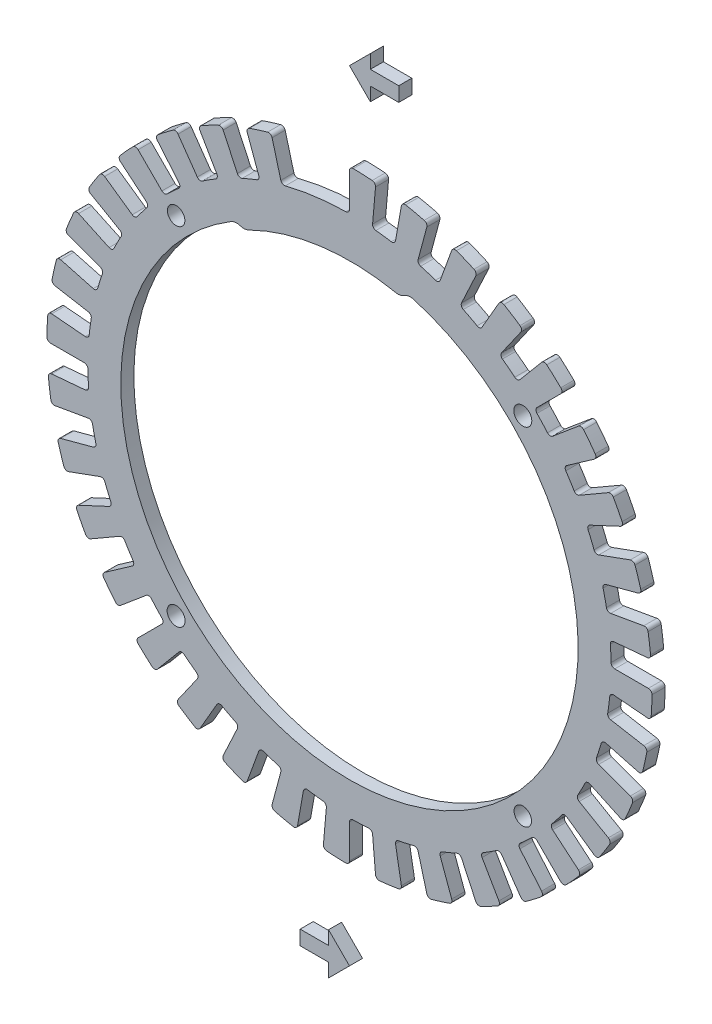
SolidWorks part; units mm, degrees
ref_plane "Front Plane" through (0, 0, 0) normal (0, 0, 1) x (1, 0, 0)
ref_plane "Top Plane" through (0, 0, 0) normal (0, 1, 0) x (1, 0, 0)
ref_plane "Right Plane" through (0, 0, 0) normal (1, 0, 0) x (0, 0, -1)
sketch "Sketch1" plane through (0, 0, 0) normal (0, 0, 1) x (1, 0, 0)
  line L0 (0, 82.7) -> (0, 71.5) construction
  line L1 (7.2078, 82.3853) -> (6.2316, 71.2279) construction
  line L2 (0, 71.5) -> (0, 0) construction
  line L3 (6.2316, 71.2279) -> (0, 0) construction
  line L4 (12.5883, 71.3918) -> (14.186, 80.4528) construction
  line L5 (12.5883, 71.3918) -> (0, 0) construction
  line L8 (0, 0) -> (47.3762, 47.3762) construction
  line L12 (50.5581, 50.5581) -> (47.3762, 47.3762) construction
  line L15 (47.3762, 47.3762) -> (44.1942, 44.1942) construction
  line L18 (7.3144, 72.1301) -> (6.3182, 72.2172) construction
  line L21 (7.3144, 72.1301) -> (7.2135, 71.1352) construction
  line L24 (12.5883, 71.3918) -> (11.6035, 71.5654) construction
  line L27 (11.6035, 71.5654) -> (11.4434, 70.5783) construction
  line L30 (1.0122, 82.6938) -> (1, 81.6939) construction
  line L33 (1, 81.6939) -> (0, 81.6939) construction
  line L36 (7.1201, 81.383) -> (6.1239, 81.4702) construction
  line L39 (6.1239, 81.4702) -> (6.1989, 82.4674) construction
  line L42 (7.1201, 81.383) -> (6.3182, 72.2172)
  line L45 (0, 81.6939) -> (0, 72.4931)
  line L48 (0, 72.4931) -> (-1, 72.4931) construction
  line L51 (-1, 72.4931) -> (-0.9862, 71.4932) construction
  line L109 (0, -82.7) -> (0, -71.5) [skipped]
  line L111 (14.3607, 81.4436) -> (12.4158, 70.4138) [skipped]
  line L115 (41.35, 71.6203) -> (35.75, 61.9208) [skipped]
  line L117 (53.1585, 63.3519) -> (45.9593, 54.7722) [skipped]
  line L118 (-63.3519, -53.1585) -> (-54.7722, -45.9593) [skipped]
  line L119 (63.3519, 53.1585) -> (54.7722, 45.9593) [skipped]
  line L121 (71.6203, 41.35) -> (61.9208, 35.75) [skipped]
  line L123 (77.7126, 28.2851) -> (67.188, 24.4544) [skipped]
  line L125 (81.4436, 14.3607) -> (70.4138, 12.4158) [skipped]
  line L127 (82.7, 0) -> (71.5, 0) [skipped]
  line L129 (81.4436, -14.3607) -> (70.4138, -12.4158) [skipped]
  line L131 (77.7126, -28.2851) -> (67.188, -24.4544) [skipped]
  line L133 (71.6203, -41.35) -> (61.9208, -35.75) [skipped]
  line L135 (63.3519, -53.1585) -> (54.7722, -45.9593) [skipped]
  line L137 (53.1585, -63.3519) -> (45.9593, -54.7722) [skipped]
  line L139 (41.35, -71.6203) -> (35.75, -61.9208) [skipped]
  line L141 (28.2851, -77.7126) -> (24.4544, -67.188) [skipped]
  line L142 (14.3607, -81.4436) -> (12.4158, -70.4138) [skipped]
  line L143 (34.9505, 74.9517) -> (30.2172, 64.801) [skipped]
  line L144 (47.4348, 67.7439) -> (41.0107, 58.5694) [skipped]
  line L145 (58.4777, 58.4777) -> (50.5581, 50.5581) [skipped]
  line L146 (67.7439, 47.4348) -> (58.5694, 41.0107) [skipped]
  line L147 (74.9517, 34.9505) -> (64.801, 30.2172) [skipped]
  line L148 (79.8821, 21.4043) -> (69.0637, 18.5056) [skipped]
  line L149 (82.3853, 7.2078) -> (71.2279, 6.2316) [skipped]
  line L150 (82.3853, -7.2078) -> (71.2279, -6.2316) [skipped]
  line L151 (79.8821, -21.4043) -> (69.0637, -18.5056) [skipped]
  line L152 (74.9517, -34.9505) -> (64.801, -30.2172) [skipped]
  line L153 (67.7439, -47.4348) -> (58.5694, -41.0107) [skipped]
  line L154 (58.4777, -58.4777) -> (50.5581, -50.5581) [skipped]
  line L155 (47.4348, -67.7439) -> (41.0107, -58.5694) [skipped]
  line L156 (34.9505, -74.9517) -> (30.2172, -64.801) [skipped]
  line L157 (21.4043, -79.8821) -> (18.5056, -69.0637) [skipped]
  line L158 (7.2078, -82.3853) -> (6.2316, -71.2279) [skipped]
  line L159 (-7.2078, -82.3853) -> (-6.2316, -71.2279) [skipped]
  line L160 (-21.4043, -79.8821) -> (-18.5056, -69.0637) [skipped]
  line L161 (-34.9505, -74.9517) -> (-30.2172, -64.801) [skipped]
  line L162 (-47.4348, -67.7439) -> (-41.0107, -58.5694) [skipped]
  line L163 (-58.4777, -58.4777) -> (-50.5581, -50.5581) [skipped]
  line L164 (-67.7439, -47.4348) -> (-58.5694, -41.0107) [skipped]
  line L165 (-74.9517, -34.9505) -> (-64.801, -30.2172) [skipped]
  line L166 (-79.8821, -21.4043) -> (-69.0637, -18.5056) [skipped]
  line L167 (-82.3853, -7.2078) -> (-71.2279, -6.2316) [skipped]
  line L168 (-82.3853, 7.2078) -> (-71.2279, 6.2316) [skipped]
  line L169 (-79.8821, 21.4043) -> (-69.0637, 18.5056) [skipped]
  line L170 (-74.9517, 34.9505) -> (-64.801, 30.2172) [skipped]
  line L171 (-67.7439, 47.4348) -> (-58.5694, 41.0107) [skipped]
  line L172 (-58.4777, 58.4777) -> (-50.5581, 50.5581) [skipped]
  line L173 (-47.4348, 67.7439) -> (-41.0107, 58.5694) [skipped]
  line L174 (-34.9505, 74.9517) -> (-30.2172, 64.801) [skipped]
  line L175 (-21.4043, 79.8821) -> (-18.5056, 69.0637) [skipped]
  line L176 (21.4043, 79.8821) -> (18.5056, 69.0637) [skipped]
  line L209 (0, 0) -> (-47.3762, -47.3762) construction
  line L210 (0, 0) -> (-47.3762, 47.3762) construction
  line L211 (0, 0) -> (47.3762, -47.3762) construction
  line L212 (14.186, 80.4528) -> (12.5883, 71.3918)
  line L213 (21.1439, 78.9102) -> (18.7626, 70.023)
  line L214 (27.941, 76.7671) -> (24.7941, 68.1212)
  line L215 (34.5253, 74.0398) -> (30.6369, 65.7011)
  line L216 (40.8469, 70.749) -> (36.2466, 62.7809)
  line L217 (46.8577, 66.9197) -> (41.5803, 59.3829)
  line L218 (52.5118, 62.5811) -> (46.5977, 55.5329)
  line L219 (57.7663, 57.7663) -> (51.2604, 51.2604)
  line L220 (62.5811, 52.5118) -> (55.5329, 46.5977)
  line L221 (66.9197, 46.8577) -> (59.3829, 41.5803)
  line L222 (70.749, 40.8469) -> (62.7809, 36.2466)
  line L223 (74.0398, 34.5253) -> (65.7011, 30.6369)
  line L224 (76.7671, 27.941) -> (68.1212, 24.7941)
  line L225 (78.9102, 21.1439) -> (70.023, 18.7626)
  line L226 (80.4528, 14.186) -> (71.3918, 12.5883)
  line L227 (81.383, 7.1201) -> (72.2172, 6.3182)
  line L228 (81.6939, 0) -> (72.4931, 0)
  line L229 (81.383, -7.1201) -> (72.2172, -6.3182)
  line L230 (80.4528, -14.186) -> (71.3918, -12.5883)
  line L231 (78.9102, -21.1439) -> (70.023, -18.7626)
  line L232 (76.7671, -27.941) -> (68.1212, -24.7941)
  line L233 (74.0398, -34.5253) -> (65.7011, -30.6369)
  line L234 (70.749, -40.8469) -> (62.7809, -36.2466)
  line L235 (66.9197, -46.8577) -> (59.3829, -41.5803)
  line L236 (62.5811, -52.5118) -> (55.5329, -46.5977)
  line L237 (57.7663, -57.7663) -> (51.2604, -51.2604)
  line L238 (52.5118, -62.5811) -> (46.5977, -55.5329)
  line L239 (46.8577, -66.9197) -> (41.5803, -59.3829)
  line L240 (40.8469, -70.749) -> (36.2466, -62.7809)
  line L241 (34.5253, -74.0398) -> (30.6369, -65.7011)
  line L242 (27.941, -76.7671) -> (24.7941, -68.1212)
  line L243 (21.1439, -78.9102) -> (18.7626, -70.023)
  line L244 (14.186, -80.4528) -> (12.5883, -71.3918)
  line L245 (7.1201, -81.383) -> (6.3182, -72.2172)
  line L246 (0, -81.6939) -> (0, -72.4931)
  line L247 (-7.1201, -81.383) -> (-6.3182, -72.2172)
  line L248 (-14.186, -80.4528) -> (-12.5883, -71.3918)
  line L249 (-21.1439, -78.9102) -> (-18.7626, -70.023)
  line L250 (-27.941, -76.7671) -> (-24.7941, -68.1212)
  line L251 (-34.5253, -74.0398) -> (-30.6369, -65.7011)
  line L252 (-40.8469, -70.749) -> (-36.2466, -62.7809)
  line L253 (-46.8577, -66.9197) -> (-41.5803, -59.3829)
  line L254 (-52.5118, -62.5811) -> (-46.5977, -55.5329)
  line L255 (-57.7663, -57.7663) -> (-51.2604, -51.2604)
  line L256 (-62.5811, -52.5118) -> (-55.5329, -46.5977)
  line L257 (-66.9197, -46.8577) -> (-59.3829, -41.5803)
  line L258 (-70.749, -40.8469) -> (-62.7809, -36.2466)
  line L259 (-74.0398, -34.5253) -> (-65.7011, -30.6369)
  line L260 (-76.7671, -27.941) -> (-68.1212, -24.7941)
  line L261 (-78.9102, -21.1439) -> (-70.023, -18.7626)
  line L262 (-80.4528, -14.186) -> (-71.3918, -12.5883)
  line L263 (-81.383, -7.1201) -> (-72.2172, -6.3182)
  line L264 (-81.6939, 0) -> (-72.4931, 0)
  line L265 (-81.383, 7.1201) -> (-72.2172, 6.3182)
  line L266 (-80.4528, 14.186) -> (-71.3918, 12.5883)
  line L267 (-78.9102, 21.1439) -> (-70.023, 18.7626)
  line L268 (-76.7671, 27.941) -> (-68.1212, 24.7941)
  line L269 (-74.0398, 34.5253) -> (-65.7011, 30.6369)
  line L270 (-70.749, 40.8469) -> (-62.7809, 36.2466)
  line L271 (-66.9197, 46.8577) -> (-59.3829, 41.5803)
  line L272 (-62.5811, 52.5118) -> (-55.5329, 46.5977)
  line L273 (-57.7663, 57.7663) -> (-51.2604, 51.2604)
  line L274 (-52.5118, 62.5811) -> (-46.5977, 55.5329)
  line L275 (-46.8577, 66.9197) -> (-41.5803, 59.3829)
  line L276 (-40.8469, 70.749) -> (-36.2466, 62.7809)
  line L277 (-34.5253, 74.0398) -> (-30.6369, 65.7011)
  line L278 (-27.941, 76.7671) -> (-24.7941, 68.1212)
  line L279 (-21.1439, 78.9102) -> (-18.7626, 70.023)
  line L280 (-0.9864, 71.4932) -> (-0.9862, 71.4932)
  line L281 (-32.3995, 53.4464) -> (-30.8444, 50.881) construction
  line L282 (-30.8444, 50.881) -> (-29.8635, 53.7161) construction
  line L283 (-29.8635, 53.7161) -> (-28.8826, 56.5512) construction
  line L284 (-28.8826, 56.5512) -> (-27.5181, 53.8795) construction
  line L285 (17.4626, 60.0109) -> (16.6244, 57.1304) construction
  line L286 (16.6244, 57.1304) -> (14.9432, 59.615) construction
  line L289 (13.262, 62.0997) -> (14.9432, 59.615) construction
  line L290 (-7.4414, 56.5227) -> (0, 0) construction
  line L291 (-27.5181, 53.8795) -> (-7.4414, 56.5227) construction
  line L292 (-7.4414, 56.5227) -> (12.6354, 59.1658) construction
  line L293 (13.262, 62.0997) -> (12.6354, 59.1658) construction
  line L294 (-28.4278, 55.6607) -> (13.0531, 61.1217) construction
  line L295 (0, 106.5536) -> (5.7145, 112.2681)
  line L296 (5.7145, 112.2681) -> (5.7145, 108.5326)
  line L297 (5.7145, 108.5326) -> (13.4712, 108.5326)
  line L298 (13.4712, 108.5326) -> (13.4712, 104.5747)
  line L299 (13.4712, 104.5747) -> (5.7145, 104.5747)
  line L300 (5.7145, 104.5747) -> (5.7145, 100.8391)
  line L301 (5.7145, 100.8391) -> (0, 106.5536)
  line L302 (0, 106.5536) -> (13.4712, 106.5536) construction
  line L303 (0, -106.5536) -> (-5.7145, -112.2681)
  line L304 (-5.7145, -112.2681) -> (-5.7145, -108.5326)
  line L305 (-5.7145, -108.5326) -> (-13.4712, -108.5326)
  line L306 (-13.4712, -108.5326) -> (-13.4712, -104.5747)
  line L307 (-13.4712, -104.5747) -> (-5.7145, -104.5747)
  line L308 (-5.7145, -104.5747) -> (-5.7145, -100.8391)
  line L309 (-5.7145, -100.8391) -> (0, -106.5536)
  circle A0 centre (0, 0) radius 82.7 construction
  arc A1 (-32.3995, 53.4464) -> (17.4626, 60.0109) centre (0, 0) ccw
  circle A73 centre (47.3762, 47.3762) radius 2.4585
  circle A74 centre (47.3762, 47.3762) radius 2.987 construction
  arc A78 (0, 71.5) -> (6.2316, 71.2279) centre (0, 0) cw construction
  arc A79 (6.3182, 72.2172) -> (7.2135, 71.1352) centre (7.3144, 72.1301) ccw
  arc A80 (11.4434, 70.5783) -> (12.5883, 71.3918) centre (11.6035, 71.5654) ccw construction
  arc A81 (7.1201, 81.383) -> (6.1989, 82.4674) centre (6.1239, 81.4702) ccw
  arc A82 (0, 81.6939) -> (1.0122, 82.6938) centre (1, 81.6939) cw
  arc A83 (6.5367, 74.7146) -> (13.0236, 73.8606) centre (0, 0) cw [skipped]
  arc A84 (7.2135, 71.1352) -> (11.4434, 70.5783) centre (0, 0) cw
  arc A85 (0, 82.7) -> (7.2078, 82.3853) centre (0, 0) cw [skipped]
  arc A86 (1.0122, 82.6938) -> (6.1989, 82.4674) centre (0, 0) cw
  arc A87 (28.2851, 77.7126) -> (34.9505, 74.9517) centre (0, 0) cw [skipped]
  arc A88 (31.6964, 67.9731) -> (37.5, 64.9519) centre (0, 0) cw [skipped]
  arc A89 (41.35, 71.6203) -> (47.4348, 67.7439) centre (0, 0) cw [skipped]
  arc A90 (43.0182, 61.4364) -> (48.2091, 57.4533) centre (0, 0) cw [skipped]
  arc A91 (53.1585, 63.3519) -> (58.4777, 58.4777) centre (0, 0) cw [skipped]
  arc A92 (53.033, 53.033) -> (57.4533, 48.2091) centre (0, 0) cw [skipped]
  arc A93 (63.3519, 53.1585) -> (67.7439, 47.4348) centre (0, 0) cw [skipped]
  arc A94 (61.4364, 43.0182) -> (64.9519, 37.5) centre (0, 0) cw [skipped]
  arc A95 (71.6203, 41.35) -> (74.9517, 34.9505) centre (0, 0) cw [skipped]
  arc A96 (67.9731, 31.6964) -> (70.4769, 25.6515) centre (0, 0) cw [skipped]
  arc A97 (77.7126, 28.2851) -> (79.8821, 21.4043) centre (0, 0) cw [skipped]
  arc A98 (72.4444, 19.4114) -> (73.8606, 13.0236) centre (0, 0) cw [skipped]
  arc A99 (81.4436, 14.3607) -> (82.3853, 7.2078) centre (0, 0) cw [skipped]
  arc A100 (74.7146, 6.5367) -> (75, 0) centre (0, 0) cw [skipped]
  arc A101 (82.7, 0) -> (82.3853, -7.2078) centre (0, 0) cw [skipped]
  arc A102 (74.7146, -6.5367) -> (73.8606, -13.0236) centre (0, 0) cw [skipped]
  arc A103 (81.4436, -14.3607) -> (79.8821, -21.4043) centre (0, 0) cw [skipped]
  arc A104 (72.4444, -19.4114) -> (70.4769, -25.6515) centre (0, 0) cw [skipped]
  arc A105 (77.7126, -28.2851) -> (74.9517, -34.9505) centre (0, 0) cw [skipped]
  arc A106 (67.9731, -31.6964) -> (64.9519, -37.5) centre (0, 0) cw [skipped]
  arc A107 (71.6203, -41.35) -> (67.7439, -47.4348) centre (0, 0) cw [skipped]
  arc A108 (61.4364, -43.0182) -> (57.4533, -48.2091) centre (0, 0) cw [skipped]
  arc A109 (63.3519, -53.1585) -> (58.4777, -58.4777) centre (0, 0) cw [skipped]
  arc A110 (53.033, -53.033) -> (48.2091, -57.4533) centre (0, 0) cw [skipped]
  arc A111 (53.1585, -63.3519) -> (47.4348, -67.7439) centre (0, 0) cw [skipped]
  arc A112 (43.0182, -61.4364) -> (37.5, -64.9519) centre (0, 0) cw [skipped]
  arc A113 (41.35, -71.6203) -> (34.9505, -74.9517) centre (0, 0) cw [skipped]
  arc A114 (31.6964, -67.9731) -> (25.6515, -70.4769) centre (0, 0) cw [skipped]
  arc A115 (28.2851, -77.7126) -> (21.4043, -79.8821) centre (0, 0) cw [skipped]
  arc A116 (19.4114, -72.4444) -> (13.0236, -73.8606) centre (0, 0) cw [skipped]
  arc A117 (14.3607, -81.4436) -> (7.2078, -82.3853) centre (0, 0) cw [skipped]
  arc A118 (6.5367, -74.7146) -> (0, -75) centre (0, 0) cw [skipped]
  arc A119 (0, -82.7) -> (-7.2078, -82.3853) centre (0, 0) cw [skipped]
  arc A120 (-6.5367, -74.7146) -> (-13.0236, -73.8606) centre (0, 0) cw [skipped]
  arc A121 (-14.3607, -81.4436) -> (-21.4043, -79.8821) centre (0, 0) cw [skipped]
  arc A122 (-28.2851, -77.7126) -> (-34.9505, -74.9517) centre (0, 0) cw [skipped]
  arc A123 (-19.4114, -72.4444) -> (-25.6515, -70.4769) centre (0, 0) cw [skipped]
  arc A124 (-31.6964, -67.9731) -> (-37.5, -64.9519) centre (0, 0) cw [skipped]
  arc A125 (-41.35, -71.6203) -> (-47.4348, -67.7439) centre (0, 0) cw [skipped]
  arc A126 (-43.0182, -61.4364) -> (-48.2091, -57.4533) centre (0, 0) cw [skipped]
  arc A127 (-53.1585, -63.3519) -> (-58.4777, -58.4777) centre (0, 0) cw [skipped]
  arc A128 (-53.033, -53.033) -> (-57.4533, -48.2091) centre (0, 0) cw [skipped]
  arc A129 (-63.3519, -53.1585) -> (-67.7439, -47.4348) centre (0, 0) cw [skipped]
  arc A130 (-61.4364, -43.0182) -> (-64.9519, -37.5) centre (0, 0) cw [skipped]
  arc A131 (-71.6203, -41.35) -> (-74.9517, -34.9505) centre (0, 0) cw [skipped]
  arc A132 (-67.9731, -31.6964) -> (-70.4769, -25.6515) centre (0, 0) cw [skipped]
  arc A133 (-77.7126, -28.2851) -> (-79.8821, -21.4043) centre (0, 0) cw [skipped]
  arc A134 (-72.4444, -19.4114) -> (-73.8606, -13.0236) centre (0, 0) cw [skipped]
  arc A135 (-81.4436, -14.3607) -> (-82.3853, -7.2078) centre (0, 0) cw [skipped]
  arc A136 (-74.7146, -6.5367) -> (-75, 0) centre (0, 0) cw [skipped]
  arc A137 (-82.7, 0) -> (-82.3853, 7.2078) centre (0, 0) cw [skipped]
  arc A138 (-74.7146, 6.5367) -> (-73.8606, 13.0236) centre (0, 0) cw [skipped]
  arc A139 (-81.4436, 14.3607) -> (-79.8821, 21.4043) centre (0, 0) cw [skipped]
  arc A140 (-72.4444, 19.4114) -> (-70.4769, 25.6515) centre (0, 0) cw [skipped]
  arc A141 (-77.7126, 28.2851) -> (-74.9517, 34.9505) centre (0, 0) cw [skipped]
  arc A142 (-67.9731, 31.6964) -> (-64.9519, 37.5) centre (0, 0) cw [skipped]
  arc A143 (-71.6203, 41.35) -> (-67.7439, 47.4348) centre (0, 0) cw [skipped]
  arc A144 (-61.4364, 43.0182) -> (-57.4533, 48.2091) centre (0, 0) cw [skipped]
  arc A145 (-63.3519, 53.1585) -> (-58.4777, 58.4777) centre (0, 0) cw [skipped]
  arc A146 (-53.033, 53.033) -> (-48.2091, 57.4533) centre (0, 0) cw [skipped]
  arc A147 (-53.1585, 63.3519) -> (-47.4348, 67.7439) centre (0, 0) cw [skipped]
  arc A148 (-43.0182, 61.4364) -> (-37.5, 64.9519) centre (0, 0) cw [skipped]
  arc A149 (-41.35, 71.6203) -> (-34.9505, 74.9517) centre (0, 0) cw [skipped]
  arc A150 (-31.6964, 67.9731) -> (-25.6515, 70.4769) centre (0, 0) cw [skipped]
  arc A151 (-28.2851, 77.7126) -> (-21.4043, 79.8821) centre (0, 0) cw [skipped]
  arc A152 (-19.4114, 72.4444) -> (-13.0236, 73.8606) centre (0, 0) cw [skipped]
  arc A153 (14.3607, 81.4436) -> (21.4043, 79.8821) centre (0, 0) cw [skipped]
  arc A154 (19.4114, 72.4444) -> (25.6515, 70.4769) centre (0, 0) cw [skipped]
  arc A155 (0, 72.4931) -> (-0.9862, 71.4932) centre (-1, 72.4931) cw
  circle A367 centre (-47.3762, -47.3762) radius 2.4585
  circle A368 centre (47.3762, -47.3762) radius 2.3813
  circle A369 centre (-47.3762, 47.3762) radius 2.3812
  circle A370 centre (0, 0) radius 71.5 construction
  arc A371 (12.5883, 71.3918) -> (11.4434, 70.5783) centre (11.6035, 71.5654) cw
  arc A372 (14.186, 80.4528) -> (15.3565, 81.2617) centre (15.1708, 80.2791) cw
  arc A373 (15.3565, 81.2617) -> (20.425, 80.1381) centre (0, 0) cw
  arc A374 (21.1439, 78.9102) -> (20.425, 80.1381) centre (20.178, 79.169) ccw
  arc A375 (18.7626, 70.023) -> (19.4564, 68.8019) centre (19.7285, 69.7641) ccw
  arc A376 (19.4564, 68.8019) -> (23.5254, 67.5189) centre (0, 0) cw
  arc A377 (24.7941, 68.1212) -> (23.5254, 67.5189) centre (23.8544, 68.4633) cw
  arc A378 (27.941, 76.7671) -> (29.2341, 77.3606) centre (28.8806, 76.4251) cw
  arc A379 (29.2341, 77.3606) -> (34.0305, 75.3738) centre (0, 0) cw
  arc A380 (34.5253, 74.0398) -> (34.0305, 75.3738) centre (33.619, 74.4624) ccw
  arc A381 (30.6369, 65.7011) -> (31.1081, 64.3781) centre (31.5432, 65.2784) ccw
  arc A382 (31.1081, 64.3781) -> (34.8925, 62.408) centre (0, 0) cw
  arc A384 (36.2466, 62.7809) -> (34.8925, 62.408) centre (35.3805, 63.2809) cw
  arc A385 (40.8469, 70.749) -> (42.2235, 71.1088) centre (41.713, 70.249) cw
  arc A386 (42.2235, 71.1088) -> (46.602, 68.3194) centre (0, 0) cw
  arc A387 (46.8577, 66.9197) -> (46.602, 68.3194) centre (46.0385, 67.4933) ccw
  arc A388 (41.5803, 59.3829) -> (41.8147, 57.9981) centre (42.3995, 58.8093) ccw
  arc A389 (41.8147, 57.9981) -> (45.1995, 55.4009) centre (0, 0) cw
  arc A390 (46.5977, 55.5329) -> (45.1995, 55.4009) centre (45.8316, 56.1757) cw
  arc A391 (52.5118, 62.5811) -> (53.93, 62.6965) centre (53.2779, 61.9384) cw
  arc A392 (53.93, 62.6965) -> (57.7576, 59.1891) centre (0, 0) cw
  arc A393 (57.7663, 57.7663) -> (57.7576, 59.1891) centre (57.0592, 58.4734) ccw
  arc A394 (51.2604, 51.2604) -> (51.2507, 49.856) centre (51.9675, 50.5533) ccw
  arc A395 (51.2507, 49.856) -> (54.133, 46.7104) centre (0, 0) cw
  arc A396 (55.5329, 46.5977) -> (54.133, 46.7104) centre (54.8902, 47.3637) cw
  arc A397 (62.5811, 52.5118) -> (63.9978, 52.3791) centre (63.2239, 51.7458) cw
  arc A398 (63.9978, 52.3791) -> (67.1582, 48.2604) centre (0, 0) cw
  arc A399 (66.9197, 46.8577) -> (67.1582, 48.2604) centre (66.3461, 47.6768) ccw
  arc A400 (59.3829, 41.5803) -> (59.1295, 40.199) centre (59.9565, 40.7612) ccw
  arc A401 (59.1295, 40.199) -> (61.4218, 36.6007) centre (0, 0) cw
  arc A402 (62.7809, 36.2466) -> (61.4218, 36.6007) centre (62.2809, 37.1126) cw
  arc A403 (70.749, 40.8469) -> (72.1211, 40.4703) centre (71.249, 39.9809) cw
  arc A404 (72.1211, 40.4703) -> (74.5182, 35.8653) centre (0, 0) cw
  arc A405 (74.0398, 34.5253) -> (74.5182, 35.8653) centre (73.6172, 35.4316) ccw
  arc A406 (65.7011, 30.6369) -> (65.2116, 29.3205) centre (66.1237, 29.7306) ccw
  arc A407 (65.2116, 29.3205) -> (66.8443, 25.3788) centre (0, 0) cw
  arc A408 (68.1212, 24.7941) -> (66.8443, 25.3788) centre (67.7792, 25.7338) cw
  arc A409 (76.7671, 27.941) -> (78.053, 27.3318) centre (77.1092, 27.0013) cw
  arc A410 (78.053, 27.3318) -> (79.6141, 22.3805) centre (0, 0) cw
  arc A411 (78.9102, 21.1439) -> (79.6141, 22.3805) centre (78.6514, 22.1099) ccw
  arc A412 (70.023, 18.7626) -> (69.3124, 17.5512) centre (70.2818, 17.7967) ccw
  arc A413 (69.3124, 17.5512) -> (70.2358, 13.3859) centre (0, 0) cw
  arc A414 (71.3918, 12.5883) -> (70.2358, 13.3859) centre (71.2181, 13.5731) cw
  arc A415 (80.4528, 14.186) -> (81.6133, 13.3628) centre (80.6264, 13.2012) cw
  arc A416 (81.6133, 13.3628) -> (82.2909, 8.2156) centre (0, 0) cw
  arc A417 (81.383, 7.1201) -> (82.2909, 8.2156) centre (81.2959, 8.1163) ccw
  arc A418 (72.2172, 6.3182) -> (71.3071, 5.2486) centre (72.3044, 5.322) ccw
  arc A419 (71.3071, 5.2486) -> (71.4932, 0.9862) centre (0, 0) cw
  arc A420 (72.4931, 0) -> (71.4932, 0.9862) centre (72.4931, 1) cw
  arc A421 (81.6939, 0) -> (82.6938, -1.0122) centre (81.6939, -1) cw
  arc A422 (82.6938, -1.0122) -> (82.4674, -6.1989) centre (0, 0) cw
  arc A423 (81.383, -7.1201) -> (82.4674, -6.1989) centre (81.4702, -6.1239) ccw
  arc A424 (72.2172, -6.3182) -> (71.1352, -7.2135) centre (72.1301, -7.3144) ccw
  arc A425 (71.1352, -7.2135) -> (70.5783, -11.4434) centre (0, 0) cw
  arc A426 (71.3918, -12.5883) -> (70.5783, -11.4434) centre (71.5654, -11.6035) cw
  arc A427 (80.4528, -14.186) -> (81.2617, -15.3565) centre (80.2791, -15.1708) cw
  arc A428 (81.2617, -15.3565) -> (80.1381, -20.425) centre (0, 0) cw
  arc A429 (78.9102, -21.1439) -> (80.1381, -20.425) centre (79.169, -20.178) ccw
  arc A430 (70.023, -18.7626) -> (68.8019, -19.4564) centre (69.7641, -19.7285) ccw
  arc A431 (68.8019, -19.4564) -> (67.5189, -23.5254) centre (0, 0) cw
  arc A432 (68.1212, -24.7941) -> (67.5189, -23.5254) centre (68.4633, -23.8544) cw
  arc A433 (76.7671, -27.941) -> (77.3606, -29.2341) centre (76.4251, -28.8806) cw
  arc A434 (77.3606, -29.2341) -> (75.3738, -34.0305) centre (0, 0) cw
  arc A435 (74.0398, -34.5253) -> (75.3738, -34.0305) centre (74.4624, -33.619) ccw
  arc A436 (65.7011, -30.6369) -> (64.3781, -31.1081) centre (65.2784, -31.5432) ccw
  arc A437 (64.3781, -31.1081) -> (62.408, -34.8925) centre (0, 0) cw
  arc A438 (62.7809, -36.2466) -> (62.408, -34.8925) centre (63.2809, -35.3805) cw
  arc A439 (70.749, -40.8469) -> (71.1088, -42.2235) centre (70.249, -41.713) cw
  arc A440 (71.1088, -42.2235) -> (68.3194, -46.602) centre (0, 0) cw
  arc A441 (66.9197, -46.8577) -> (68.3194, -46.602) centre (67.4933, -46.0385) ccw
  arc A442 (59.3829, -41.5803) -> (57.9981, -41.8147) centre (58.8093, -42.3995) ccw
  arc A443 (57.9981, -41.8147) -> (55.4009, -45.1995) centre (0, 0) cw
  arc A444 (55.5329, -46.5977) -> (55.4009, -45.1995) centre (56.1757, -45.8316) cw
  arc A445 (62.5811, -52.5118) -> (62.6965, -53.93) centre (61.9384, -53.2779) cw
  arc A446 (62.6965, -53.93) -> (59.1891, -57.7576) centre (0, 0) cw
  arc A447 (57.7663, -57.7663) -> (59.1891, -57.7576) centre (58.4734, -57.0592) ccw
  arc A448 (51.2604, -51.2604) -> (49.856, -51.2507) centre (50.5533, -51.9675) ccw
  arc A449 (49.856, -51.2507) -> (46.7104, -54.133) centre (0, 0) cw
  arc A450 (46.5977, -55.5329) -> (46.7104, -54.133) centre (47.3637, -54.8902) cw
  arc A451 (52.5118, -62.5811) -> (52.3791, -63.9978) centre (51.7458, -63.2239) cw
  arc A452 (52.3791, -63.9978) -> (48.2604, -67.1582) centre (0, 0) cw
  arc A453 (46.8577, -66.9197) -> (48.2604, -67.1582) centre (47.6768, -66.3461) ccw
  arc A454 (41.5803, -59.3829) -> (40.199, -59.1295) centre (40.7612, -59.9565) ccw
  arc A455 (40.199, -59.1295) -> (36.6007, -61.4218) centre (0, 0) cw
  arc A456 (36.2466, -62.7809) -> (36.6007, -61.4218) centre (37.1126, -62.2809) cw
  arc A457 (40.8469, -70.749) -> (40.4703, -72.1211) centre (39.9809, -71.249) cw
  arc A458 (40.4703, -72.1211) -> (35.8653, -74.5182) centre (0, 0) cw
  arc A459 (34.5253, -74.0398) -> (35.8653, -74.5182) centre (35.4316, -73.6172) ccw
  arc A460 (30.6369, -65.7011) -> (29.3205, -65.2116) centre (29.7306, -66.1237) ccw
  arc A461 (29.3205, -65.2116) -> (25.3788, -66.8443) centre (0, 0) cw
  arc A462 (24.7941, -68.1212) -> (25.3788, -66.8443) centre (25.7338, -67.7792) cw
  arc A463 (27.941, -76.7671) -> (27.3318, -78.053) centre (27.0013, -77.1092) cw
  arc A464 (27.3318, -78.053) -> (22.3805, -79.6141) centre (0, 0) cw
  arc A465 (21.1439, -78.9102) -> (22.3805, -79.6141) centre (22.1099, -78.6514) ccw
  arc A466 (18.7626, -70.023) -> (17.5512, -69.3124) centre (17.7967, -70.2818) ccw
  arc A467 (17.5512, -69.3124) -> (13.3859, -70.2358) centre (0, 0) cw
  arc A468 (12.5883, -71.3918) -> (13.3859, -70.2358) centre (13.5731, -71.2181) cw
  arc A469 (14.186, -80.4528) -> (13.3628, -81.6133) centre (13.2012, -80.6264) cw
  arc A470 (13.3628, -81.6133) -> (8.2156, -82.2909) centre (0, 0) cw
  arc A471 (7.1201, -81.383) -> (8.2156, -82.2909) centre (8.1163, -81.2959) ccw
  arc A472 (6.3182, -72.2172) -> (5.2486, -71.3071) centre (5.322, -72.3044) ccw
  arc A473 (5.2486, -71.3071) -> (0.9862, -71.4932) centre (0, 0) cw
  arc A474 (0, -72.4931) -> (0.9862, -71.4932) centre (1, -72.4931) cw
  arc A475 (0, -81.6939) -> (-1.0122, -82.6938) centre (-1, -81.6939) cw
  arc A476 (-1.0122, -82.6938) -> (-6.1989, -82.4674) centre (0, 0) cw
  arc A477 (-7.1201, -81.383) -> (-6.1989, -82.4674) centre (-6.1239, -81.4702) ccw
  arc A478 (-6.3182, -72.2172) -> (-7.2135, -71.1352) centre (-7.3144, -72.1301) ccw
  arc A479 (-7.2135, -71.1352) -> (-11.4434, -70.5783) centre (0, 0) cw
  arc A480 (-12.5883, -71.3918) -> (-11.4434, -70.5783) centre (-11.6035, -71.5654) cw
  arc A481 (-14.186, -80.4528) -> (-15.3565, -81.2617) centre (-15.1708, -80.2791) cw
  arc A482 (-15.3565, -81.2617) -> (-20.425, -80.1381) centre (0, 0) cw
  arc A483 (-21.1439, -78.9102) -> (-20.425, -80.1381) centre (-20.178, -79.169) ccw
  arc A484 (-18.7626, -70.023) -> (-19.4564, -68.8019) centre (-19.7285, -69.7641) ccw
  arc A485 (-19.4564, -68.8019) -> (-23.5254, -67.5189) centre (0, 0) cw
  arc A486 (-24.7941, -68.1212) -> (-23.5254, -67.5189) centre (-23.8544, -68.4633) cw
  arc A487 (-27.941, -76.7671) -> (-29.2341, -77.3606) centre (-28.8806, -76.4251) cw
  arc A488 (-29.2341, -77.3606) -> (-34.0305, -75.3738) centre (0, 0) cw
  arc A489 (-34.5253, -74.0398) -> (-34.0305, -75.3738) centre (-33.619, -74.4624) ccw
  arc A490 (-30.6369, -65.7011) -> (-31.1081, -64.3781) centre (-31.5432, -65.2784) ccw
  arc A491 (-31.1081, -64.3781) -> (-34.8925, -62.408) centre (0, 0) cw
  arc A492 (-36.2466, -62.7809) -> (-34.8925, -62.408) centre (-35.3805, -63.2809) cw
  arc A493 (-40.8469, -70.749) -> (-42.2235, -71.1088) centre (-41.713, -70.249) cw
  arc A494 (-42.2235, -71.1088) -> (-46.602, -68.3194) centre (0, 0) cw
  arc A495 (-46.8577, -66.9197) -> (-46.602, -68.3194) centre (-46.0385, -67.4933) ccw
  arc A496 (-41.5803, -59.3829) -> (-41.8147, -57.9981) centre (-42.3995, -58.8093) ccw
  arc A497 (-41.8147, -57.9981) -> (-45.1995, -55.4009) centre (0, 0) cw
  arc A498 (-46.5977, -55.5329) -> (-45.1995, -55.4009) centre (-45.8316, -56.1757) cw
  arc A499 (-52.5118, -62.5811) -> (-53.93, -62.6965) centre (-53.2779, -61.9384) cw
  arc A500 (-53.93, -62.6965) -> (-57.7576, -59.1891) centre (0, 0) cw
  arc A501 (-57.7663, -57.7663) -> (-57.7576, -59.1891) centre (-57.0592, -58.4734) ccw
  arc A502 (-51.2604, -51.2604) -> (-51.2507, -49.856) centre (-51.9675, -50.5533) ccw
  arc A503 (-51.2507, -49.856) -> (-54.133, -46.7104) centre (0, 0) cw
  arc A504 (-55.5329, -46.5977) -> (-54.133, -46.7104) centre (-54.8902, -47.3637) cw
  arc A505 (-62.5811, -52.5118) -> (-63.9978, -52.3791) centre (-63.2239, -51.7458) cw
  arc A506 (-63.9978, -52.3791) -> (-67.1582, -48.2604) centre (0, 0) cw
  arc A507 (-66.9197, -46.8577) -> (-67.1582, -48.2604) centre (-66.3461, -47.6768) ccw
  arc A508 (-59.3829, -41.5803) -> (-59.1295, -40.199) centre (-59.9565, -40.7612) ccw
  arc A509 (-59.1295, -40.199) -> (-61.4218, -36.6007) centre (0, 0) cw
  arc A510 (-62.7809, -36.2466) -> (-61.4218, -36.6007) centre (-62.2809, -37.1126) cw
  arc A511 (-70.749, -40.8469) -> (-72.1211, -40.4703) centre (-71.249, -39.9809) cw
  arc A512 (-72.1211, -40.4703) -> (-74.5182, -35.8653) centre (0, 0) cw
  arc A513 (-74.0398, -34.5253) -> (-74.5182, -35.8653) centre (-73.6172, -35.4316) ccw
  arc A514 (-65.7011, -30.6369) -> (-65.2116, -29.3205) centre (-66.1237, -29.7306) ccw
  arc A515 (-65.2116, -29.3205) -> (-66.8443, -25.3788) centre (0, 0) cw
  arc A516 (-68.1212, -24.7941) -> (-66.8443, -25.3788) centre (-67.7792, -25.7338) cw
  arc A517 (-76.7671, -27.941) -> (-78.053, -27.3318) centre (-77.1092, -27.0013) cw
  arc A518 (-78.053, -27.3318) -> (-79.6141, -22.3805) centre (0, 0) cw
  arc A519 (-78.9102, -21.1439) -> (-79.6141, -22.3805) centre (-78.6514, -22.1099) ccw
  arc A520 (-70.023, -18.7626) -> (-69.3124, -17.5512) centre (-70.2818, -17.7967) ccw
  arc A521 (-69.3124, -17.5512) -> (-70.2358, -13.3859) centre (0, 0) cw
  arc A522 (-71.3918, -12.5883) -> (-70.2358, -13.3859) centre (-71.2181, -13.5731) cw
  arc A523 (-80.4528, -14.186) -> (-81.6133, -13.3628) centre (-80.6264, -13.2012) cw
  arc A524 (-81.6133, -13.3628) -> (-82.2909, -8.2156) centre (0, 0) cw
  arc A525 (-81.383, -7.1201) -> (-82.2909, -8.2156) centre (-81.2959, -8.1163) ccw
  arc A526 (-72.2172, -6.3182) -> (-71.3071, -5.2486) centre (-72.3044, -5.322) ccw
  arc A527 (-71.3071, -5.2486) -> (-71.4932, -0.9862) centre (0, 0) cw
  arc A528 (-72.4931, 0) -> (-71.4932, -0.9862) centre (-72.4931, -1) cw
  arc A529 (-81.6939, 0) -> (-82.6938, 1.0122) centre (-81.6939, 1) cw
  arc A530 (-82.6938, 1.0122) -> (-82.4674, 6.1989) centre (0, 0) cw
  arc A531 (-81.383, 7.1201) -> (-82.4674, 6.1989) centre (-81.4702, 6.1239) ccw
  arc A532 (-72.2172, 6.3182) -> (-71.1352, 7.2135) centre (-72.1301, 7.3144) ccw
  arc A533 (-71.1352, 7.2135) -> (-70.5783, 11.4434) centre (0, 0) cw
  arc A534 (-71.3918, 12.5883) -> (-70.5783, 11.4434) centre (-71.5654, 11.6035) cw
  arc A535 (-80.4528, 14.186) -> (-81.2617, 15.3565) centre (-80.2791, 15.1708) cw
  arc A536 (-81.2617, 15.3565) -> (-80.1381, 20.425) centre (0, 0) cw
  arc A537 (-78.9102, 21.1439) -> (-80.1381, 20.425) centre (-79.169, 20.178) ccw
  arc A538 (-70.023, 18.7626) -> (-68.8019, 19.4564) centre (-69.7641, 19.7285) ccw
  arc A539 (-68.8019, 19.4564) -> (-67.5189, 23.5254) centre (0, 0) cw
  arc A540 (-68.1212, 24.7941) -> (-67.5189, 23.5254) centre (-68.4633, 23.8544) cw
  arc A541 (-76.7671, 27.941) -> (-77.3606, 29.2341) centre (-76.4251, 28.8806) cw
  arc A542 (-77.3606, 29.2341) -> (-75.3738, 34.0305) centre (0, 0) cw
  arc A543 (-74.0398, 34.5253) -> (-75.3738, 34.0305) centre (-74.4624, 33.619) ccw
  arc A544 (-65.7011, 30.6369) -> (-64.3781, 31.1081) centre (-65.2784, 31.5432) ccw
  arc A545 (-64.3781, 31.1081) -> (-62.408, 34.8925) centre (0, 0) cw
  arc A546 (-62.7809, 36.2466) -> (-62.408, 34.8925) centre (-63.2809, 35.3805) cw
  arc A547 (-70.749, 40.8469) -> (-71.1088, 42.2235) centre (-70.249, 41.713) cw
  arc A548 (-71.1088, 42.2235) -> (-68.3194, 46.602) centre (0, 0) cw
  arc A549 (-66.9197, 46.8577) -> (-68.3194, 46.602) centre (-67.4933, 46.0385) ccw
  arc A550 (-59.3829, 41.5803) -> (-57.9981, 41.8147) centre (-58.8093, 42.3995) ccw
  arc A551 (-57.9981, 41.8147) -> (-55.4009, 45.1995) centre (0, 0) cw
  arc A552 (-55.5329, 46.5977) -> (-55.4009, 45.1995) centre (-56.1757, 45.8316) cw
  arc A553 (-62.5811, 52.5118) -> (-62.6965, 53.93) centre (-61.9384, 53.2779) cw
  arc A554 (-62.6965, 53.93) -> (-59.1891, 57.7576) centre (0, 0) cw
  arc A555 (-57.7663, 57.7663) -> (-59.1891, 57.7576) centre (-58.4734, 57.0592) ccw
  arc A556 (-51.2604, 51.2604) -> (-49.856, 51.2507) centre (-50.5533, 51.9675) ccw
  arc A557 (-49.856, 51.2507) -> (-46.7104, 54.133) centre (0, 0) cw
  arc A558 (-46.5977, 55.5329) -> (-46.7104, 54.133) centre (-47.3637, 54.8902) cw
  arc A559 (-52.5118, 62.5811) -> (-52.3791, 63.9978) centre (-51.7458, 63.2239) cw
  arc A560 (-52.3791, 63.9978) -> (-48.2604, 67.1582) centre (0, 0) cw
  arc A561 (-46.8577, 66.9197) -> (-48.2604, 67.1582) centre (-47.6768, 66.3461) ccw
  arc A562 (-41.5803, 59.3829) -> (-40.199, 59.1295) centre (-40.7612, 59.9565) ccw
  arc A563 (-40.199, 59.1295) -> (-36.6007, 61.4218) centre (0, 0) cw
  arc A564 (-36.2466, 62.7809) -> (-36.6007, 61.4218) centre (-37.1126, 62.2809) cw
  arc A565 (-40.8469, 70.749) -> (-40.4703, 72.1211) centre (-39.9809, 71.249) cw
  arc A566 (-40.4703, 72.1211) -> (-35.8653, 74.5182) centre (0, 0) cw
  arc A567 (-34.5253, 74.0398) -> (-35.8653, 74.5182) centre (-35.4316, 73.6172) ccw
  arc A568 (-30.6369, 65.7011) -> (-29.3205, 65.2116) centre (-29.7306, 66.1237) ccw
  arc A569 (-29.3205, 65.2116) -> (-25.3788, 66.8443) centre (0, 0) cw
  arc A570 (-24.7941, 68.1212) -> (-25.3788, 66.8443) centre (-25.7338, 67.7792) cw
  arc A571 (-27.941, 76.7671) -> (-27.3318, 78.053) centre (-27.0013, 77.1092) cw
  arc A572 (-27.3318, 78.053) -> (-22.3805, 79.6141) centre (0, 0) cw
  arc A573 (-21.1439, 78.9102) -> (-22.3805, 79.6141) centre (-22.1099, 78.6514) ccw
  arc A574 (-18.7626, 70.023) -> (-17.5512, 69.3124) centre (-17.7967, 70.2818) ccw
  arc A575 (-17.5512, 69.3124) -> (-13.3859, 70.2358) centre (0, 0) cw
  arc A576 (-13.3859, 70.2358) -> (-0.9864, 71.4932) centre (0, 0) cw
  arc A577 (-29.8635, 53.7161) -> (-32.3995, 53.4464) centre (-30.8444, 50.881) ccw
  arc A578 (-29.8635, 53.7161) -> (-27.5181, 53.8795) centre (-28.8826, 56.5512) ccw
  arc A579 (17.4626, 60.0109) -> (14.9432, 59.615) centre (16.6244, 57.1304) ccw
  arc A580 (14.9432, 59.615) -> (12.6354, 59.1658) centre (13.262, 62.0997) cw
  circle A582 centre (0, 0) radius 62.5 construction
  arc A586 (-27.5181, 53.8795) -> (12.6354, 59.1658) centre (0.3099, -2.3542) cw
  point P3 (-28.4278, 55.6607)
  point P29 (0, 0)
  point P133 (13.0531, 61.1217)
  point P252 (0, 0)
  point P703 (0, 0)
  point P728 (0, 0)
  point P763 (0, 0)
  dimension "D2" = 165.4
  dimension "D7" = 4.917
  dimension "D8" = 5.974
  dimension "D12" = 1
  dimension "D14" = 11.2
  dimension "D15" = 11.2
  dimension "D17" = 2
  dimension "D20" = 4.7625
  dimension "D21" = 4.917
  dimension "D22" = 4.7625
  dimension "D3" = 5
  dimension "D4" = 67
  dimension "D6" = 45
  dimension "D10" = 67
  dimension "D11" = 5
  dimension "D9" = 4.5
  dimension "D16" = 7.5
  dimension "D18" = 40.5
  dimension "D19" = 3
  dimension "D5" = 35
  dimension "D13" = 35
  dimension "D23" = 2
extrude "Boss-Extrude1" add sketch "Sketch1" along normal blind 3.5719
